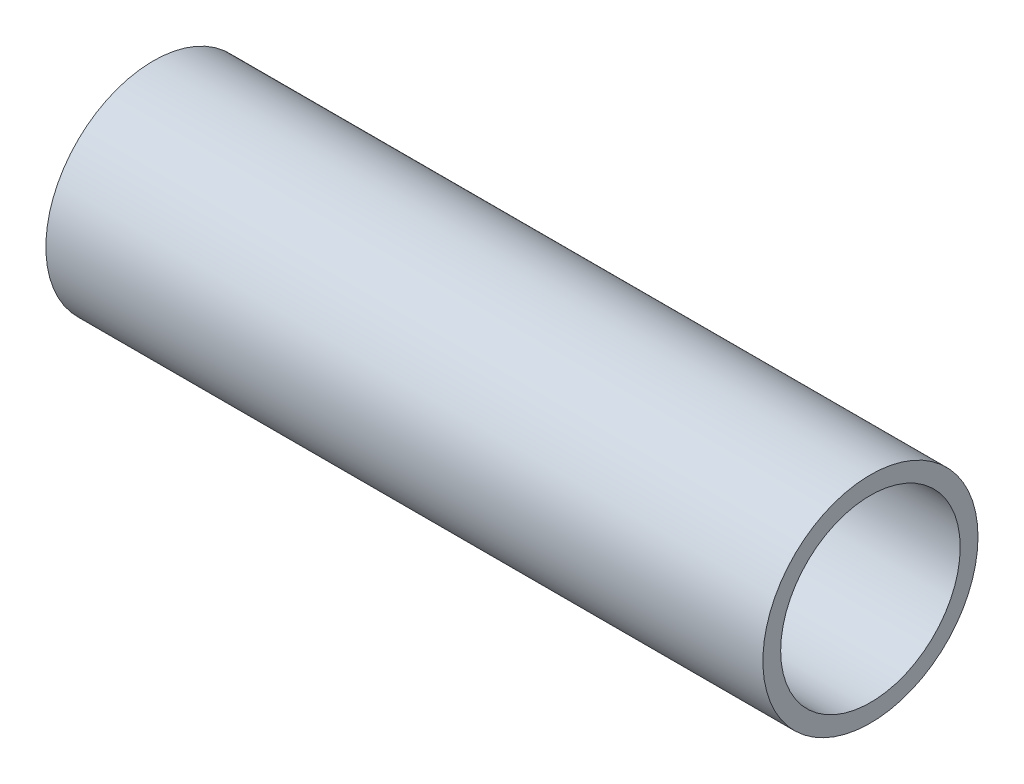
SolidWorks part; units mm, degrees
ref_plane "Front Plane" through (0, 0, 0) normal (0, 0, 1) x (1, 0, 0)
ref_plane "Top Plane" through (0, 0, 0) normal (0, 1, 0) x (1, 0, 0)
ref_plane "Right Plane" through (0, 0, 0) normal (1, 0, 0) x (0, 0, -1)
sketch "Sketch1" plane through (0, 0, 0) normal (1, 0, 0) x (0, 0, -1)
  circle A0 centre (0, 0) radius 3.9751
  circle A1 centre (0, 0) radius 4.7625
  dimension "D1" = 9.525
  dimension "D2" = 7.9502
extrude "Boss-Extrude1" add sketch "Sketch1" along normal blind 31.75
